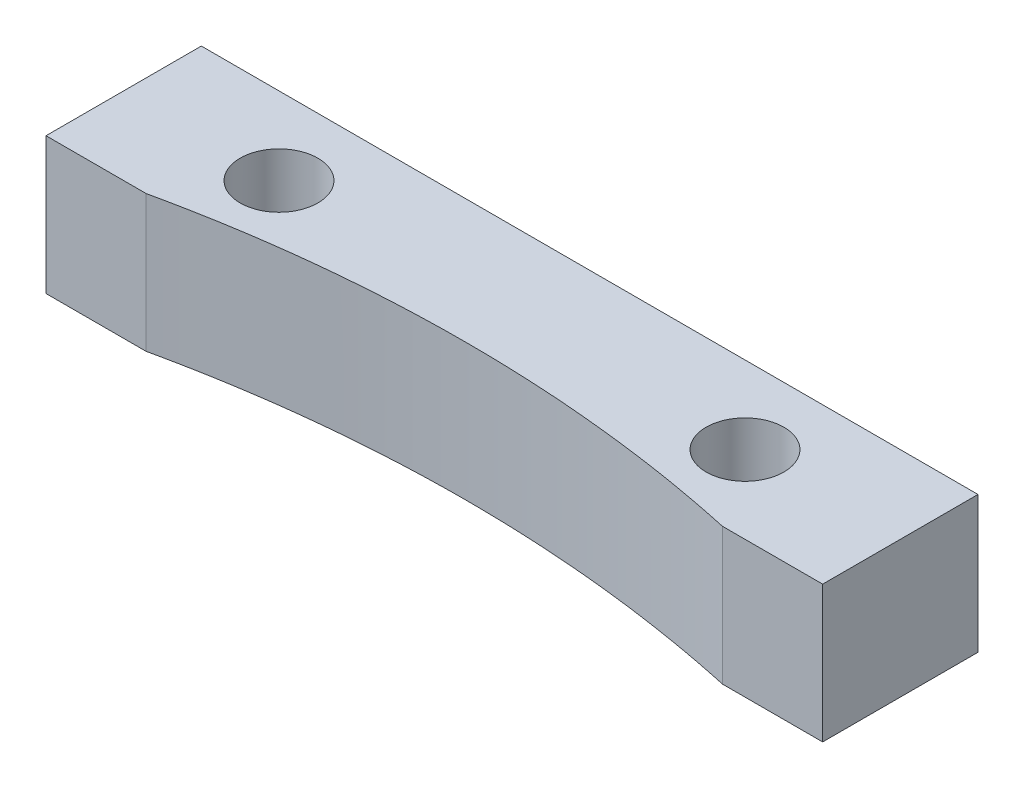
SolidWorks part; units mm, degrees
material "PLA"
ref_plane "Front Plane" through (0, 0, 0) normal (0, 0, 1) x (1, 0, 0)
ref_plane "Top Plane" through (0, 0, 0) normal (0, 1, 0) x (1, 0, 0)
ref_plane "Right Plane" through (0, 0, 0) normal (1, 0, 0) x (0, 0, -1)
ref_plane "Plane1" through (0, 0, 0) normal (0, -1, 0) x (1, 0, 0)
sketch "Sketch1" plane through (0, 0, 0) normal (0, -1, 0) x (1, 0, 0)
  line L0 (-5, -2.5) -> (20, -2.5)
  line L1 (20, -2.5) -> (20, 2.5)
  line L2 (20, 2.5) -> (16.7736, 2.5)
  line L3 (16.7736, 2.5) -> (16.1204, 2.3627)
  line L4 (16.1204, 2.3627) -> (15.4651, 2.2354)
  line L5 (15.4651, 2.2354) -> (14.8079, 2.1183)
  line L6 (14.8079, 2.1183) -> (14.1491, 2.0112)
  line L7 (14.1491, 2.0112) -> (13.4886, 1.9142)
  line L8 (13.4886, 1.9142) -> (12.8268, 1.8274)
  line L9 (12.8268, 1.8274) -> (12.1637, 1.7507)
  line L10 (12.1637, 1.7507) -> (11.4995, 1.6843)
  line L11 (11.4995, 1.6843) -> (10.8343, 1.628)
  line L12 (10.8343, 1.628) -> (10.1684, 1.5819)
  line L13 (10.1684, 1.5819) -> (9.5019, 1.5461)
  line L14 (9.5019, 1.5461) -> (8.8348, 1.5205)
  line L15 (8.8348, 1.5205) -> (8.1675, 1.5051)
  line L16 (8.1675, 1.5051) -> (7.5, 1.5)
  line L17 (7.5, 1.5) -> (6.8325, 1.5051)
  line L18 (6.8325, 1.5051) -> (6.1652, 1.5205)
  line L19 (6.1652, 1.5205) -> (5.4981, 1.5461)
  line L20 (5.4981, 1.5461) -> (4.8316, 1.5819)
  line L21 (4.8316, 1.5819) -> (4.1657, 1.628)
  line L22 (4.1657, 1.628) -> (3.5005, 1.6843)
  line L23 (3.5005, 1.6843) -> (2.8363, 1.7507)
  line L24 (2.8363, 1.7507) -> (2.1732, 1.8274)
  line L25 (2.1732, 1.8274) -> (1.5114, 1.9142)
  line L26 (1.5114, 1.9142) -> (0.8509, 2.0112)
  line L27 (0.8509, 2.0112) -> (0.1921, 2.1183)
  line L28 (0.1921, 2.1183) -> (-0.4651, 2.2354)
  line L29 (-0.4651, 2.2354) -> (-1.1204, 2.3627)
  line L30 (-1.1204, 2.3627) -> (-1.7736, 2.5)
  line L31 (-1.7736, 2.5) -> (-5, 2.5)
  line L32 (-5, 2.5) -> (-5, -2.5)
  line L33 (14.7457, -1.2239) -> (14.6354, -1.1957)
  line L34 (14.6354, -1.1957) -> (14.5282, -1.1576)
  line L35 (14.5282, -1.1576) -> (14.4249, -1.1099)
  line L36 (14.4249, -1.1099) -> (14.3264, -1.053)
  line L37 (14.3264, -1.053) -> (14.2334, -0.9873)
  line L38 (14.2334, -0.9873) -> (14.1468, -0.9135)
  line L39 (14.1468, -0.9135) -> (14.0673, -0.8322)
  line L40 (14.0673, -0.8322) -> (13.9955, -0.7439)
  line L41 (13.9955, -0.7439) -> (13.932, -0.6495)
  line L42 (13.932, -0.6495) -> (13.8773, -0.5497)
  line L43 (13.8773, -0.5497) -> (13.832, -0.4453)
  line L44 (13.832, -0.4453) -> (13.7964, -0.3372)
  line L45 (13.7964, -0.3372) -> (13.7707, -0.2264)
  line L46 (13.7707, -0.2264) -> (13.7552, -0.1137)
  line L47 (13.7552, -0.1137) -> (13.75, 0)
  line L48 (13.75, 0) -> (13.7552, 0.1137)
  line L49 (13.7552, 0.1137) -> (13.7707, 0.2264)
  line L50 (13.7707, 0.2264) -> (13.7964, 0.3372)
  line L51 (13.7964, 0.3372) -> (13.832, 0.4453)
  line L52 (13.832, 0.4453) -> (13.8773, 0.5497)
  line L53 (13.8773, 0.5497) -> (13.932, 0.6495)
  line L54 (13.932, 0.6495) -> (13.9955, 0.7439)
  line L55 (13.9955, 0.7439) -> (14.0673, 0.8322)
  line L56 (14.0673, 0.8322) -> (14.1468, 0.9135)
  line L57 (14.1468, 0.9135) -> (14.2334, 0.9873)
  line L58 (14.2334, 0.9873) -> (14.3264, 1.053)
  line L59 (14.3264, 1.053) -> (14.4249, 1.1099)
  line L60 (14.4249, 1.1099) -> (14.5282, 1.1576)
  line L61 (14.5282, 1.1576) -> (14.6354, 1.1957)
  line L62 (14.6354, 1.1957) -> (14.7457, 1.2239)
  line L63 (14.7457, 1.2239) -> (14.858, 1.2419)
  line L64 (14.858, 1.2419) -> (14.9715, 1.2497)
  line L65 (14.9715, 1.2497) -> (15.0853, 1.2471)
  line L66 (15.0853, 1.2471) -> (15.1984, 1.2342)
  line L67 (15.1984, 1.2342) -> (15.3098, 1.211)
  line L68 (15.3098, 1.211) -> (15.4186, 1.1778)
  line L69 (15.4186, 1.1778) -> (15.524, 1.1349)
  line L70 (15.524, 1.1349) -> (15.625, 1.0825)
  line L71 (15.625, 1.0825) -> (15.7208, 1.0212)
  line L72 (15.7208, 1.0212) -> (15.8107, 0.9514)
  line L73 (15.8107, 0.9514) -> (15.8939, 0.8738)
  line L74 (15.8939, 0.8738) -> (15.9696, 0.7889)
  line L75 (15.9696, 0.7889) -> (16.0374, 0.6974)
  line L76 (16.0374, 0.6974) -> (16.0965, 0.6002)
  line L77 (16.0965, 0.6002) -> (16.1465, 0.498)
  line L78 (16.1465, 0.498) -> (16.187, 0.3917)
  line L79 (16.187, 0.3917) -> (16.2177, 0.2821)
  line L80 (16.2177, 0.2821) -> (16.2384, 0.1702)
  line L81 (16.2384, 0.1702) -> (16.2487, 0.0569)
  line L82 (16.2487, 0.0569) -> (16.2487, -0.0569)
  line L83 (16.2487, -0.0569) -> (16.2384, -0.1702)
  line L84 (16.2384, -0.1702) -> (16.2177, -0.2821)
  line L85 (16.2177, -0.2821) -> (16.187, -0.3917)
  line L86 (16.187, -0.3917) -> (16.1465, -0.498)
  line L87 (16.1465, -0.498) -> (16.0965, -0.6002)
  line L88 (16.0965, -0.6002) -> (16.0374, -0.6974)
  line L89 (16.0374, -0.6974) -> (15.9696, -0.7889)
  line L90 (15.9696, -0.7889) -> (15.8939, -0.8738)
  line L91 (15.8939, -0.8738) -> (15.8107, -0.9514)
  line L92 (15.8107, -0.9514) -> (15.7208, -1.0212)
  line L93 (15.7208, -1.0212) -> (15.625, -1.0825)
  line L94 (15.625, -1.0825) -> (15.524, -1.1349)
  line L95 (15.524, -1.1349) -> (15.4186, -1.1778)
  line L96 (15.4186, -1.1778) -> (15.3098, -1.211)
  line L97 (15.3098, -1.211) -> (15.1984, -1.2342)
  line L98 (15.1984, -1.2342) -> (15.0853, -1.2471)
  line L99 (15.0853, -1.2471) -> (14.9715, -1.2497)
  line L100 (14.9715, -1.2497) -> (14.858, -1.2419)
  line L101 (14.858, -1.2419) -> (14.7457, -1.2239)
  line L102 (0.4186, -1.1778) -> (0.3098, -1.211)
  line L103 (0.3098, -1.211) -> (0.1984, -1.2342)
  line L104 (0.1984, -1.2342) -> (0.0853, -1.2471)
  line L105 (0.0853, -1.2471) -> (-0.0285, -1.2497)
  line L106 (-0.0285, -1.2497) -> (-0.142, -1.2419)
  line L107 (-0.142, -1.2419) -> (-0.2543, -1.2239)
  line L108 (-0.2543, -1.2239) -> (-0.3646, -1.1957)
  line L109 (-0.3646, -1.1957) -> (-0.4718, -1.1576)
  line L110 (-0.4718, -1.1576) -> (-0.5751, -1.1099)
  line L111 (-0.5751, -1.1099) -> (-0.6736, -1.053)
  line L112 (-0.6736, -1.053) -> (-0.7666, -0.9873)
  line L113 (-0.7666, -0.9873) -> (-0.8532, -0.9135)
  line L114 (-0.8532, -0.9135) -> (-0.9327, -0.8322)
  line L115 (-0.9327, -0.8322) -> (-1.0045, -0.7439)
  line L116 (-1.0045, -0.7439) -> (-1.068, -0.6495)
  line L117 (-1.068, -0.6495) -> (-1.1227, -0.5497)
  line L118 (-1.1227, -0.5497) -> (-1.168, -0.4453)
  line L119 (-1.168, -0.4453) -> (-1.2036, -0.3372)
  line L120 (-1.2036, -0.3372) -> (-1.2293, -0.2264)
  line L121 (-1.2293, -0.2264) -> (-1.2448, -0.1137)
  line L122 (-1.2448, -0.1137) -> (-1.25, 0)
  line L123 (-1.25, 0) -> (-1.2448, 0.1137)
  line L124 (-1.2448, 0.1137) -> (-1.2293, 0.2264)
  line L125 (-1.2293, 0.2264) -> (-1.2036, 0.3372)
  line L126 (-1.2036, 0.3372) -> (-1.168, 0.4453)
  line L127 (-1.168, 0.4453) -> (-1.1227, 0.5497)
  line L128 (-1.1227, 0.5497) -> (-1.068, 0.6495)
  line L129 (-1.068, 0.6495) -> (-1.0045, 0.7439)
  line L130 (-1.0045, 0.7439) -> (-0.9327, 0.8322)
  line L131 (-0.9327, 0.8322) -> (-0.8532, 0.9135)
  line L132 (-0.8532, 0.9135) -> (-0.7666, 0.9873)
  line L133 (-0.7666, 0.9873) -> (-0.6736, 1.053)
  line L134 (-0.6736, 1.053) -> (-0.5751, 1.1099)
  line L135 (-0.5751, 1.1099) -> (-0.4718, 1.1576)
  line L136 (-0.4718, 1.1576) -> (-0.3646, 1.1957)
  line L137 (-0.3646, 1.1957) -> (-0.2543, 1.2239)
  line L138 (-0.2543, 1.2239) -> (-0.142, 1.2419)
  line L139 (-0.142, 1.2419) -> (-0.0285, 1.2497)
  line L140 (-0.0285, 1.2497) -> (0.0853, 1.2471)
  line L141 (0.0853, 1.2471) -> (0.1984, 1.2342)
  line L142 (0.1984, 1.2342) -> (0.3098, 1.211)
  line L143 (0.3098, 1.211) -> (0.4186, 1.1778)
  line L144 (0.4186, 1.1778) -> (0.524, 1.1349)
  line L145 (0.524, 1.1349) -> (0.625, 1.0825)
  line L146 (0.625, 1.0825) -> (0.7209, 1.0212)
  line L147 (0.7209, 1.0212) -> (0.8107, 0.9514)
  line L148 (0.8107, 0.9514) -> (0.8939, 0.8738)
  line L149 (0.8939, 0.8738) -> (0.9696, 0.7889)
  line L150 (0.9696, 0.7889) -> (1.0374, 0.6974)
  line L151 (1.0374, 0.6974) -> (1.0965, 0.6002)
  line L152 (1.0965, 0.6002) -> (1.1465, 0.498)
  line L153 (1.1465, 0.498) -> (1.187, 0.3917)
  line L154 (1.187, 0.3917) -> (1.2177, 0.2821)
  line L155 (1.2177, 0.2821) -> (1.2384, 0.1702)
  line L156 (1.2384, 0.1702) -> (1.2487, 0.0569)
  line L157 (1.2487, 0.0569) -> (1.2487, -0.0569)
  line L158 (1.2487, -0.0569) -> (1.2384, -0.1702)
  line L159 (1.2384, -0.1702) -> (1.2177, -0.2821)
  line L160 (1.2177, -0.2821) -> (1.187, -0.3917)
  line L161 (1.187, -0.3917) -> (1.1465, -0.498)
  line L162 (1.1465, -0.498) -> (1.0965, -0.6002)
  line L163 (1.0965, -0.6002) -> (1.0374, -0.6974)
  line L164 (1.0374, -0.6974) -> (0.9696, -0.7889)
  line L165 (0.9696, -0.7889) -> (0.8939, -0.8738)
  line L166 (0.8939, -0.8738) -> (0.8107, -0.9514)
  line L167 (0.8107, -0.9514) -> (0.7209, -1.0212)
  line L168 (0.7209, -1.0212) -> (0.625, -1.0825)
  line L169 (0.625, -1.0825) -> (0.524, -1.1349)
  line L170 (0.524, -1.1349) -> (0.4186, -1.1778)
extrude "Boss-Extrude1" add sketch "Sketch1" against normal blind 4.4
sketch "Sketch2" plane through (0, 0, 0) normal (0, -1, 0) x (1, 0, 0)
  line L0 (-1.7736, 2.5) -> (16.7736, 2.5)
  arc A0 (-1.7736, 2.5) -> (16.7736, 2.5) centre (7.5, 45) ccw
  circle A1 centre (15, 0) radius 1.25
  circle A2 centre (0, 0) radius 1.25
extrude "Cut-Extrude1" cut sketch "Sketch2" against normal through all
